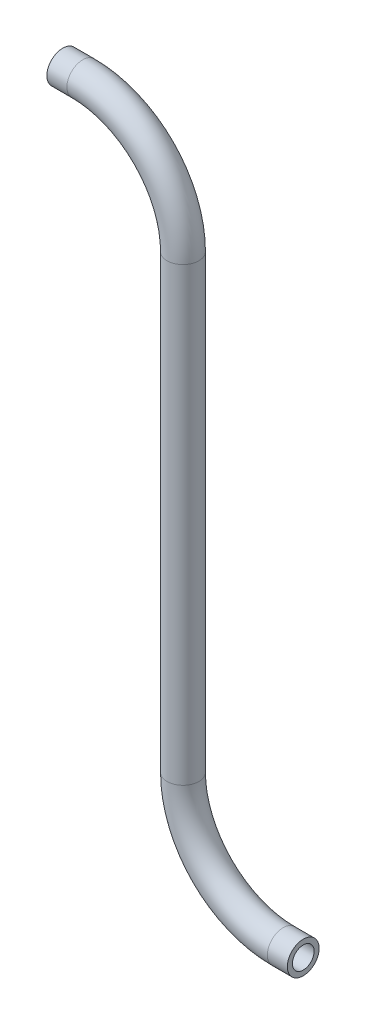
SolidWorks part; units mm, degrees
ref_plane "Piano frontale" through (0, 0, 0) normal (0, 0, 1) x (1, 0, 0)
ref_plane "Piano superiore" through (0, 0, 0) normal (0, 1, 0) x (1, 0, 0)
ref_plane "Piano destro" through (0, 0, 0) normal (1, 0, 0) x (0, 0, -1)
sketch "Schizzo1" plane through (0, 0, 0) normal (0, 0, 1) x (1, 0, 0)
  line L0 (0, 10) -> (0, 55)
  line L1 (-10, 65) -> (-12, 65)
  line L2 (10, 0) -> (12, 0)
  arc A0 (0, 55) -> (-10, 65) centre (-10, 55) ccw
  arc A1 (0, 10) -> (10, 0) centre (10, 10) ccw
  point P7 (0, 65)
  point P10 (0, 0)
  dimension "D3" = 10
  dimension "D1" = 65
  dimension "D2" = 12
  dimension "D4" = 90
  dimension "D5" = 90
sweep "Sweep-Sottile1" add path "Schizzo1" circular profile diameter 3.17 parameters "D1"=0.5, "D3"=3.17
